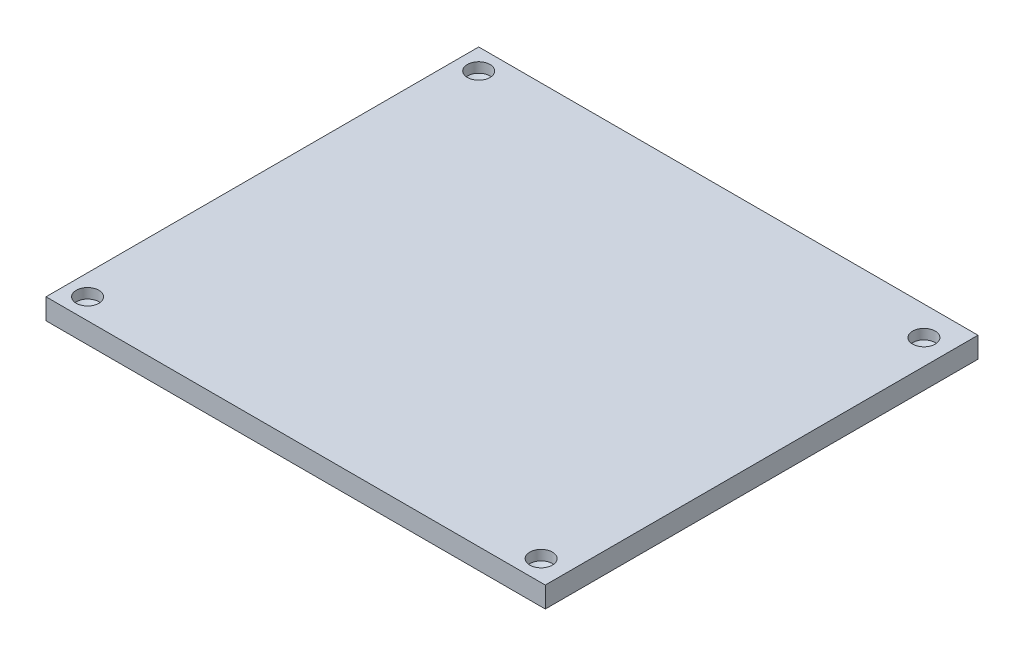
SolidWorks part; units mm, degrees
ref_plane "Front Plane" through (0, 0, 0) normal (0, 0, 1) x (1, 0, 0)
ref_plane "Top Plane" through (0, 0, 0) normal (0, 1, 0) x (1, 0, 0)
ref_plane "Right Plane" through (0, 0, 0) normal (1, 0, 0) x (0, 0, -1)
sketch "Sketch1" plane through (0, 0, 0) normal (0, 1, 0) x (1, 0, 0)
  line L0 (-38.1, 33.02) -> (38.1, 33.02)
  line L1 (-38.1, 33.02) -> (38.1, 33.02) construction
  line L2 (-38.1, 33.02) -> (-38.1, -33.02) construction
  line L3 (-38.1, -33.02) -> (38.1, -33.02) construction
  line L4 (38.1, 33.02) -> (38.1, -33.02) construction
  line L5 (-38.1, 33.02) -> (38.1, -33.02) construction
  line L6 (-38.1, -33.02) -> (38.1, 33.02) construction
  line L7 (38.1, 33.02) -> (38.1, -33.02)
  line L8 (-38.1, -33.02) -> (38.1, -33.02)
  line L9 (-38.1, 33.02) -> (-38.1, -33.02)
  point P0 (0, 0)
  dimension "D1" = 76.2
  dimension "D2" = 66.04
extrude "Boss-Extrude1" add sketch "Sketch1" along normal blind 3.175
sketch "Sketch3" plane through (0, 3.175, 0) normal (0, 1, 0) x (1, 0, 0)
  line L0 (-38.354, 33.274) -> (38.354, 33.274)
  line L1 (-38.1, 33.02) -> (38.1, 33.02) construction
  line L2 (-38.1, 33.02) -> (-38.1, -33.02) construction
  line L3 (-38.1, -33.02) -> (38.1, -33.02) construction
  line L4 (38.1, 33.02) -> (38.1, -33.02) construction
  line L5 (-38.1, 33.02) -> (38.1, -33.02) construction
  line L6 (-38.1, -33.02) -> (38.1, 33.02) construction
  line L7 (38.354, 33.274) -> (38.354, -33.274)
  line L8 (-38.354, -33.274) -> (38.354, -33.274)
  line L9 (-38.354, 33.274) -> (-38.354, -33.274)
  point P0 (0, 0)
  dimension "D1" = 76.2
  dimension "D2" = 66.04
  dimension "D3" = 0.254
extrude "Cut-Extrude1" cut sketch "Sketch3" against normal blind 4.699 rebuild error yes
hole_wizard "#4 Clearance Hole1" positions "Sketch7" profile "Sketch6" hole size "#4" standard "ANSI Inch"
sketch "Sketch7" plane through (0, 11.811, 0) normal (0, 1, 0) x (1, 0, 0)
  line L1 (-38.1, 33.02) -> (38.1, 33.02) construction
  line L2 (-38.1, 33.02) -> (-38.1, -33.02) construction
  line L3 (-38.1, -33.02) -> (38.1, -33.02) construction
  line L4 (38.1, 33.02) -> (38.1, -33.02) construction
  line L5 (-38.1, 33.02) -> (38.1, -33.02) construction
  line L6 (-38.1, -33.02) -> (38.1, 33.02) construction
  point P0 (-34.925, 29.845)
  point P2 (34.29, 28.575)
  point P4 (34.29, -29.845)
  point P6 (-34.925, -29.845)
  dimension "D1" = 76.2
  dimension "D2" = 66.04
  dimension "D3" = 3.175
  dimension "D4" = 62.865
  dimension "D5" = 3.175
  dimension "D6" = 3.175
  dimension "D7" = 3.175
  dimension "D8" = 72.39
  dimension "D9" = 72.39
  dimension "D10" = 61.595
sketch "Sketch6" plane through (-34.925, 11.811, -29.845) normal (1, 0, 0) x (0, 0, 1)
  line L0 (0, 0) -> (0, 11.1978)
  line L1 (0, 11.1978) -> (1.7272, 10.16)
  line L2 (1.7272, 10.16) -> (1.7272, 0)
  line L5 (1.7272, 0) -> (0, 0)
  line L10 (0, 11.1978) -> (-1.7272, 10.16) construction
  line L11 (0, -6.35) -> (0, 107.95) construction
  dimension "Hole Dia." = 3.4544
  dimension "Hole Depth" = 10.16
  dimension "Drill Angle" = 118
